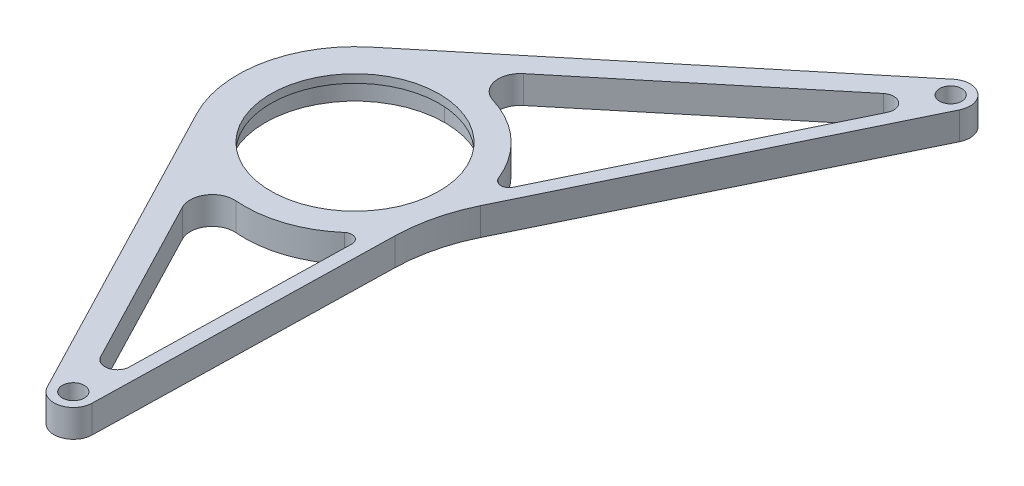
SolidWorks part; units mm, degrees
material "7075-T6, Płyta (SS)"
ref_plane "Płaszczyzna przednia" through (0, 0, 0) normal (0, 0, 1) x (1, 0, 0)
ref_plane "Płaszczyzna górna" through (0, 0, 0) normal (0, 1, 0) x (1, 0, 0)
ref_plane "Płaszczyzna prawa" through (0, 0, 0) normal (1, 0, 0) x (0, 0, -1)
sketch "Szkic2" plane through (0, 0, 0) normal (0, 1, 0) x (1, 0, 0)
  line L0 (1608.86, -402.2611) -> (1581.7, -273.0855) construction
  line L1 (1581.7, -273.0855) -> (1674.65, -150.3) construction
  line L2 (1543.9935, -292.6934) -> (1602.6495, -405.4907)
  line L5 (1670.1931, -144.9022) -> (1554.6402, -240.3133)
  line L6 (1618.513, -281.9764) -> (1615.8583, -402.4154)
  line L7 (1618.513, -281.9764) -> (1680.9473, -153.3568)
  circle A0 centre (1608.86, -402.2611) radius 4
  circle A2 centre (1581.7, -273.0855) radius 32.5
  circle A3 centre (1674.65, -150.3) radius 4
  arc A5 (1554.6402, -240.3133) -> (1543.9935, -292.6934) centre (1581.7, -273.0855) ccw
  circle A6 centre (1581.7, -273.0855) radius 37 construction
  arc A7 (1602.6495, -405.4907) -> (1615.8583, -402.4154) centre (1608.86, -402.2611) ccw
  arc A9 (1680.9473, -153.3568) -> (1670.1931, -144.9022) centre (1674.65, -150.3) ccw
  dimension "D3" = 8
  dimension "D4" = 7
  dimension "D5" = 8
  dimension "D6" = 14
  dimension "D7" = 65
  dimension "D12" = 85
  dimension "D13" = 74
  dimension "D1" = 154
  dimension "D2" = 132
  dimension "D8" = 131
  dimension "D9" = 1674.65
  dimension "D10" = 150.3
  dimension "D11" = 1608.86
extrude "Dodanie-wyciągnięcie1" add sketch "Szkic2" along normal blind 10
sketch "Szkic3" plane through (0, 10, 0) normal (0, 1, 0) x (1, 0, 0)
  line L0 (1543.9935, -292.6934) -> (1602.6495, -405.4907) construction
  line L2 (1602.8257, -386.3221) -> (1562.0626, -307.9334)
  line L3 (1543.9935, -292.6934) -> (1602.6495, -405.4907) construction
  line L5 (1662.0255, -162.0208) -> (1575.3429, -233.5939)
  line L6 (1670.1931, -144.9022) -> (1554.6402, -240.3133) construction
  line L8 (1674.65, -150.3) -> (1581.7, -273.0855) construction
  line L9 (1620.9681, -265.4689) -> (1668.6541, -167.232)
  line L11 (1611.2551, -384.3596) -> (1613.1633, -297.7849)
  line L13 (1618.513, -281.9764) -> (1680.9473, -153.3568) construction
  line L14 (1670.1931, -144.9022) -> (1554.6402, -240.3133) construction
  line L16 (1615.8583, -402.4154) -> (1618.513, -281.9764) construction
  circle A2 centre (1581.7, -273.0855) radius 40
  arc A5 (1611.2551, -384.3596) -> (1602.8257, -386.3221) centre (1606.789, -384.2611) cw
  circle A6 centre (1608.86, -402.2611) radius 4 construction
  arc A7 (1668.6541, -167.232) -> (1662.0255, -162.0208) centre (1664.7726, -165.3478) ccw
  dimension "D1" = 9
  dimension "D2" = 80
  dimension "D7" = 18
  dimension "D4" = 18
  dimension "D3" = 5
  dimension "D5" = 5
  dimension "D6" = 8
extrude "Wytnij-wyciągnięcie1" cut sketch "Szkic3" against normal blind 4 contours A7 L8 A2 L9 | L8 A7 L5 A2 | A5 L11 A2 L2 region at (1596.1287, 10, 338.9944) region at (1618.5423, 10, 208.7331) region at (1635.1967, 10, 217.3647)
extrude "Wytnij-wyciągnięcie2" cut sketch "Szkic3<3>" along normal through all from offset 10 contours L8 A7 L5 A2 | A7 L8 A2 L9 | A5 L11 A2 L2 region at (1596.1287, 10, 338.9944) region at (1618.5423, 10, 208.7331) region at (1635.1967, 10, 217.3647) offset against normal yes
sketch "Szkic3<3>" plane through (0, 10, 0) normal (0, 1, 0) x (1, 0, 0) same geometry as "Szkic3"
sketch "Szkic4" plane through (0, 0, 0) normal (0, -1, 0) x (-1, 0, 0)
  circle A0 centre (-1581.7, -273.0855) radius 32.5
  circle A1 centre (-1581.7, -273.0855) radius 30.5
  dimension "D1" = 65
  dimension "D2" = 61
extrude "Dodanie-wyciągnięcie2" add sketch "Szkic4" along normal blind 3 from offset 10 offset against normal yes
split line "Linia podziałowa1"
ref_point "Punkt1"
fillet "Zaokrąglenie1" radius 60 1 edges at (1618.513, 5, 281.9764)
fillet "Zaokrąglenie2" radius 8 2 edges at (1562.0626, 5, 307.9334) (1575.3429, 5, 233.5939)
fillet "Zaokrąglenie3" radius 3 2 edges at (1613.1633, 5, 297.7849) (1620.9681, 5, 265.4689)
